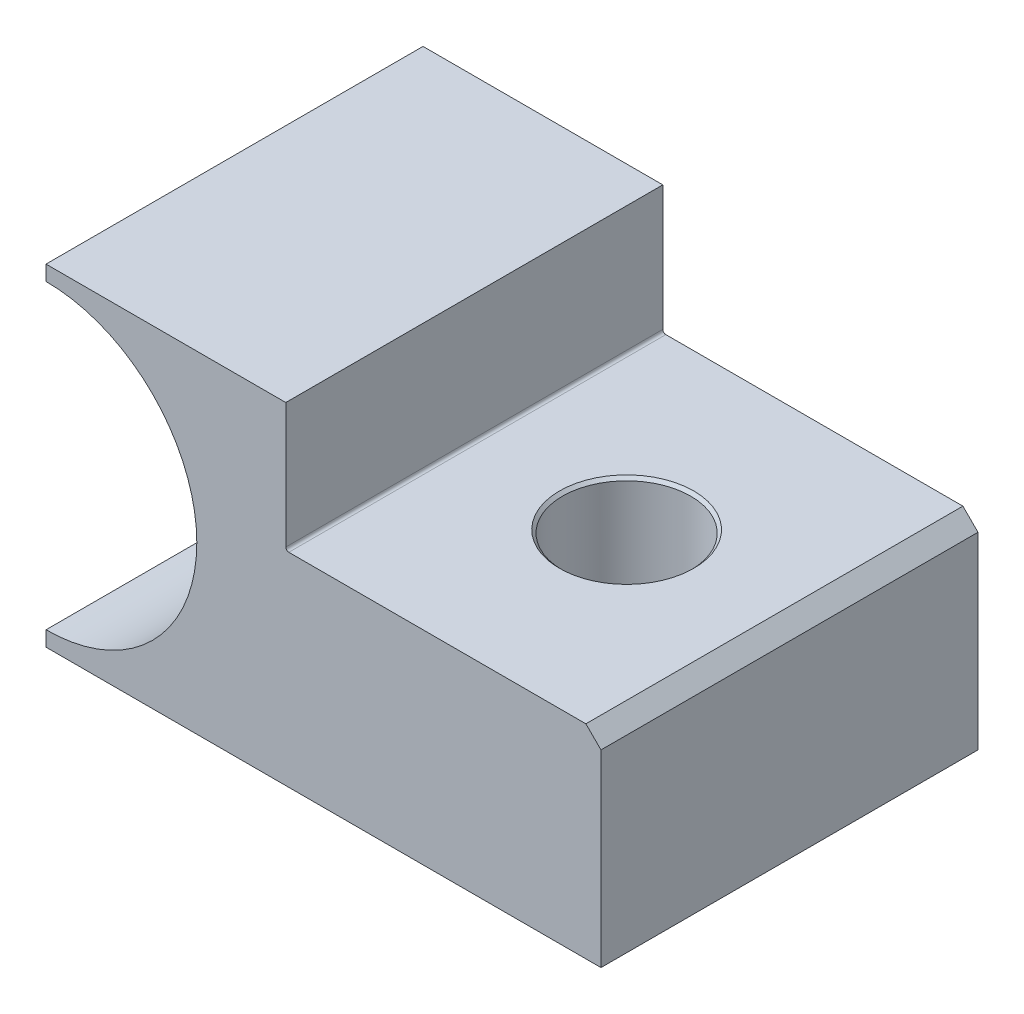
SolidWorks part; units mm, degrees
material "AISI Type A2 Tool Steel Custom"
ref_plane "Front Plane" through (0, 0, 0) normal (0, 0, 1) x (1, 0, 0)
ref_plane "Top Plane" through (0, 0, 0) normal (0, 1, 0) x (1, 0, 0)
ref_plane "Right Plane" through (0, 0, 0) normal (1, 0, 0) x (0, 0, -1)
sketch "Sketch1" plane through (0, 0, 0) normal (0, 0, 1) x (1, 0, 0)
  line L4 (46.736, 0) -> (46.736, 17.145)
  line L6 (20.193, 27.94) -> (20.193, 17.145)
  line L7 (20.193, 17.145) -> (46.736, 17.145)
  line L9 (0, 26.67) -> (0, 27.94)
  line L10 (0, 27.94) -> (20.193, 27.94)
  line L11 (0, 1.27) -> (0, 0)
  line L12 (0, 0) -> (46.736, 0)
  arc A1 (0, 1.27) -> (0, 26.67) centre (0, 13.97) ccw
  point P0 (-45.1736, 24.538)
  dimension "D2" = 25.4
  dimension "D1" = 10.795
  dimension "D3" = 17.145
  dimension "D4" = 46.736
  dimension "D5" = 26.543
  dimension "D6" = 1.27
  dimension "D7" = 1.27
extrude "Boss-Extrude1" add sketch "Sketch1" along normal blind 31.75
sketch "Sketch5" plane through (0, 17.145, 0) normal (0, 1, 0) x (1, 0, 0)
  line L2 (0, -31.75) -> (0, 0) construction
  point P0 (33.02, -15.875)
  point P12 (0, -15.875)
  dimension "D1" = 33.02
hole_wizard "X (0.397) Diameter Hole1" positions "Sketch5" profile "Sketch4" hole size "X" standard "ANSI Inch" end condition through all
sketch "Sketch4" plane through (33.02, 17.145, 15.875) normal (1, 0, 0) x (0, 0, 1)
  line L0 (0, 0) -> (0, 17.145)
  line L1 (0, 17.145) -> (5.3975, 17.145)
  line L2 (5.3975, 17.145) -> (5.3975, 0)
  line L5 (5.3975, 0) -> (0, 0)
  line L11 (0, -6.35) -> (0, 107.95) construction
  dimension "Thru Hole Dia." = 10.795
  dimension "Thru Hole Depth" = 17.145
chamfer "Chamfer1" distance 1.27 angle 45 1 edges at (46.736, 17.145, 15.875)
chamfer "Chamfer2" distance 0.254 angle 45 1 edges at (33.02, 17.145, 21.2725)
fillet "Fillet1" radius 0.254 1 edges at (20.193, 17.145, 15.875)
